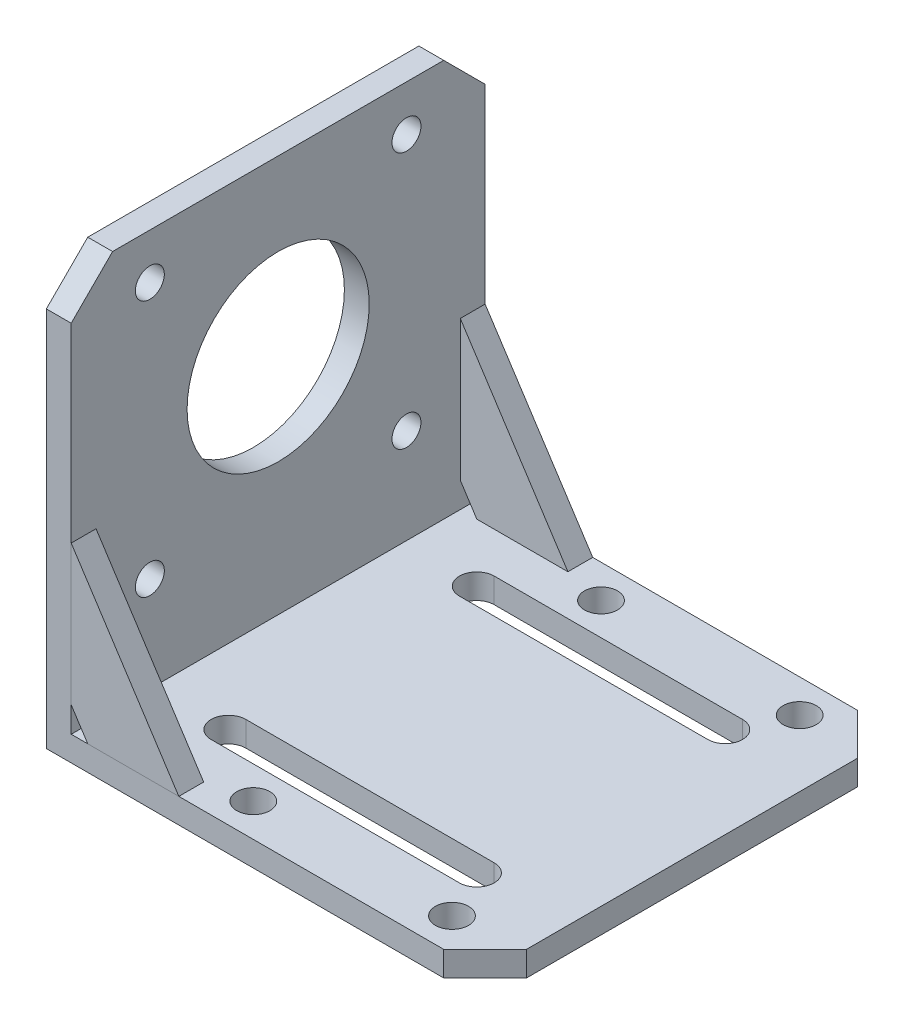
SolidWorks part; units mm, degrees
ref_plane "Front" through (0, 0, 0) normal (0, 0, 1) x (1, 0, 0)
ref_plane "Top" through (0, 0, 0) normal (0, 1, 0) x (1, 0, 0)
ref_plane "Right" through (0, 0, 0) normal (1, 0, 0) x (0, 0, -1)
sketch "Esquisse1" plane through (0, 0, 0) normal (0, 0, 1) x (1, 0, 0)
  line L0 (0, 0) -> (53, 0)
  line L1 (53, 0) -> (53, 3)
  line L2 (53, 3) -> (3, 3)
  line L3 (3, 3) -> (3, 51)
  line L4 (3, 51) -> (0, 51)
  line L5 (0, 51) -> (0, 0)
  dimension "D1" = 53
  dimension "D2" = 51
  dimension "D3" = 3
  dimension "D4" = 3
extrude "Boss.-Extru.1" add sketch "Esquisse1" along normal blind 50
sketch "Esquisse2" plane through (0, 0, 0) normal (-1, 0, 0) x (0, 0, 1)
  line L0 (25, 51) -> (25, 0) construction
  line L1 (50, 51) -> (0, 51) construction
  line L2 (50, 0) -> (0, 0) construction
  line L3 (25, 30) -> (0, 30) construction
  line L4 (0, 51) -> (0, 0) construction
  circle A0 centre (9.5, 45.5) radius 1.75
  circle A1 centre (40.5, 45.5) radius 1.75
  circle A2 centre (40.5, 14.5) radius 1.75
  circle A3 centre (9.5, 14.5) radius 1.75
  circle A4 centre (25, 30) radius 11
  dimension "D2" = 31
  dimension "D3" = 31
  dimension "D4" = 3.5
  dimension "D5" = 22
  dimension "D1" = 21
extrude "Enlèv. mat.-Extru.1" cut sketch "Esquisse2" against normal through all
chamfer "Chanfrein1" distance 5 angle 45 4 edges at (53, 1.5, 50) (53, 1.5, 0) (1.5, 51, 0) (1.5, 51, 50)
sketch "Esquisse3" plane through (0, 0, 0) normal (0, -1, 0) x (1, 0, 0)
  line L0 (0, 25) -> (53, 25) construction
  line L1 (0, 50) -> (0, 0) construction
  line L2 (53, 45) -> (53, 5) construction
  line L3 (12, 40) -> (42, 40) construction
  line L4 (12, 42.1) -> (42, 42.1)
  line L5 (12, 37.9) -> (42, 37.9)
  line L6 (12, 10) -> (42, 10) construction
  line L7 (12, 7.9) -> (42, 7.9)
  line L8 (12, 12.1) -> (42, 12.1)
  arc A0 (12, 42.1) -> (12, 37.9) centre (12, 40) ccw
  arc A1 (42, 37.9) -> (42, 42.1) centre (42, 40) ccw
  arc A2 (12, 7.9) -> (12, 12.1) centre (12, 10) cw
  arc A3 (42, 12.1) -> (42, 7.9) centre (42, 10) cw
  point P8 (27, 40)
  point P15 (27, 10)
  dimension "D1" = 30
  dimension "D2" = 11
  dimension "D3" = 4.2
  dimension "D4" = 15
extrude "Enlèv. mat.-Extru.2" cut sketch "Esquisse3" against normal through all
sketch "Esquisse4" plane through (0, 0, 50) normal (0, 0, 1) x (1, 0, 0)
  line L0 (3, 23) -> (16, 3)
  line L1 (3, 3) -> (3, 46) construction
  line L2 (48, 3) -> (3, 3) construction
  line L3 (16, 3) -> (5, 3)
  line L4 (5, 3) -> (3, 6.0769)
  line L5 (3, 6.0769) -> (3, 23)
  dimension "D1" = 20
  dimension "D2" = 13
  dimension "D3" = 2
extrude "Boss.-Extru.2" add sketch "Esquisse4" against normal blind 3 separate body
extrude "Boss.-Extru.3" add sketch "Esquisse4<2>" along normal blind 3 from vertex separate body starting at point (3, 3, 0)
sketch "Esquisse4<2>" plane through (0, 0, 50) normal (0, 0, 1) x (1, 0, 0) same geometry as "Esquisse4"
sketch "Esquisse5" plane through (0, 3, 0) normal (0, 1, 0) x (1, 0, 0)
  line L0 (45, 0) -> (45, -50) construction
  line L1 (48, 0) -> (3, 0) construction
  line L2 (48, -50) -> (3, -50) construction
  line L3 (45, -25) -> (33, -25) construction
  line L4 (33, -25) -> (33, -18.1443) construction
  line L5 (21, 0) -> (21, -50) construction
  line L6 (53, -45) -> (53, -5) construction
  circle A0 centre (45, -4) radius 2
  circle A1 centre (45, -46) radius 2
  circle A2 centre (21, -46) radius 2
  circle A3 centre (21, -4) radius 2
  dimension "D1" = 4
  dimension "D2" = 42
  dimension "D3" = 24
  dimension "D4" = 8
extrude "Enlèv. mat.-Extru.3" cut sketch "Esquisse5" against normal through all
